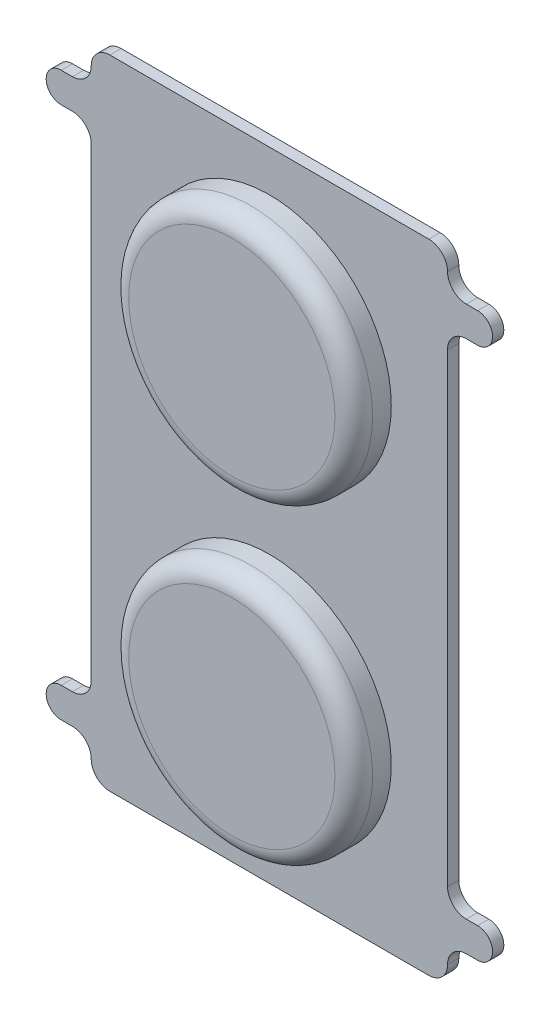
SolidWorks part; units mm, degrees
ref_plane "前基準面" through (0, 0, 0) normal (0, 0, 1) x (1, 0, 0)
ref_plane "上基準面" through (0, 0, 0) normal (0, 1, 0) x (1, 0, 0)
ref_plane "右基準面" through (0, 0, 0) normal (1, 0, 0) x (0, 0, -1)
ref_axis "基準軸1" through (0, -55, 0) along (0, 1, 0)
ref_axis "基準軸2" through (-88.99, 0, 0) along (1, 0, 0)
ref_axis "基準軸3" through (0, 0, 55) along (0, 0, -1)
sketch "草圖1" plane through (0, 0, 0) normal (0, 0, 1) x (1, 0, 0)
  line L0 (-47.5, 67) -> (-47.5, -67)
  line L1 (-47.5, 85) -> (47.5, 85)
  line L2 (-47.5, 85) -> (-47.5, 75)
  line L3 (-47.5, -85) -> (47.5, -85)
  line L4 (47.5, 85) -> (47.5, 75)
  line L5 (55, 0) -> (-55, 0) construction
  line L6 (0, -55) -> (0, 55) construction
  line L7 (55.5, 75) -> (47.5, 75)
  line L8 (55.5, 67) -> (47.5, 67)
  line L9 (47.5, 67) -> (47.5, -67)
  line L10 (55.5, -67) -> (47.5, -67)
  line L11 (55.5, -75) -> (47.5, -75)
  line L12 (-55.5, -75) -> (-47.5, -75)
  line L13 (-55.5, -67) -> (-47.5, -67)
  line L14 (-55.5, 67) -> (-47.5, 67)
  line L15 (-55.5, 75) -> (-47.5, 75)
  line L16 (-47.5, -75) -> (-47.5, -85)
  line L17 (47.5, -75) -> (47.5, -85)
  arc A4 (55.5, 67) -> (55.5, 75) centre (55.5, 71) ccw
  arc A5 (55.5, -67) -> (55.5, -75) centre (55.5, -71) cw
  arc A6 (-55.5, -67) -> (-55.5, -75) centre (-55.5, -71) ccw
  arc A7 (-55.5, 67) -> (-55.5, 75) centre (-55.5, 71) cw
  dimension "D1" = 95
  dimension "D2" = 170
  dimension "D3" = 85
  dimension "D4" = 47.5
  dimension "D5" = 8
  dimension "D6" = 8
  dimension "D7" = 10
extrude "填料-伸長1" add sketch "草圖1" along normal blind 3
fillet "圓角1" radius 5 12 edges at (-47.5, -67, 1.5) (-47.5, -75, 1.5) (-47.5, 67, 1.5) (-47.5, 75, 1.5) (47.5, 67, 1.5) (47.5, 75, 1.5) (47.5, -67, 1.5) (47.5, -75, 1.5) (47.5, -85, 1.5) (-47.5, -85, 1.5) (-47.5, 85, 1.5) (47.5, 85, 1.5)
sketch "草圖2" plane through (0, 0, 3) normal (0, 0, 1) x (1, 0, 0)
  line L0 (0, -55) -> (0, 55) construction
  line L1 (55, 0) -> (-55, 0) construction
  circle A0 centre (0, 41.5) radius 32.5
  circle A1 centre (0, -41.5) radius 32.5
  dimension "D1" = 65
  dimension "D2" = 41.5
extrude "填料-伸長2" add sketch "草圖2" along normal blind 10
fillet "圓角2" radius 5 2 edges at (-32.5, -41.5, 13) (32.5, 41.5, 13)
